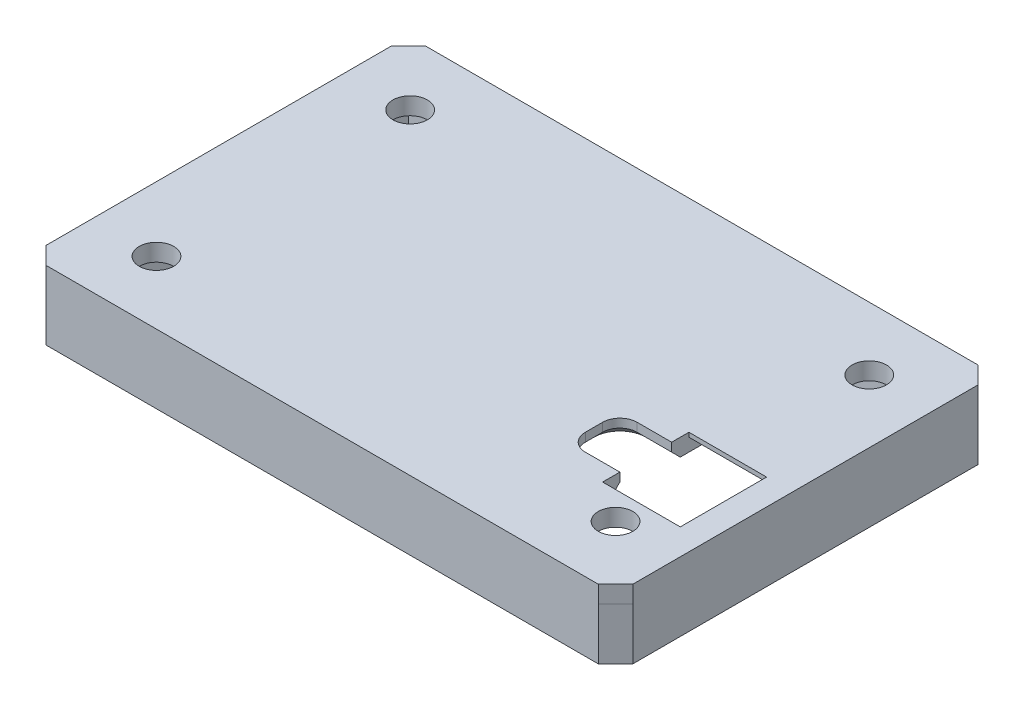
SolidWorks part; units mm, degrees
ref_plane "Front Plane" through (0, 0, 0) normal (0, 0, 1) x (1, 0, 0)
ref_plane "Top Plane" through (0, 0, 0) normal (0, 1, 0) x (1, 0, 0)
ref_plane "Right Plane" through (0, 0, 0) normal (1, 0, 0) x (0, 0, -1)
sketch "Sketch1" plane through (0, 0, 0) normal (0, 1, 0) x (1, 0, 0)
  line L1 (-29.6081, 14.5531) -> (38.3919, 14.5531)
  line L2 (-29.6081, 14.5531) -> (-29.6081, -29.4469)
  line L3 (-29.6081, -29.4469) -> (38.3919, -29.4469)
  line L4 (38.3919, 14.5531) -> (38.3919, -29.4469)
  dimension "D1" = 68
  dimension "D2" = 44
extrude "Boss-Extrude1" add sketch "Sketch1" along normal blind 2
sketch "Sketch2" plane through (0, 2, 0) normal (0, 1, 0) x (1, 0, 0)
  line L0 (38.3919, 14.5531) -> (-29.6081, 14.5531) construction
  line L1 (-29.6081, 14.5531) -> (-29.6081, -29.4469) construction
  line L2 (38.3919, -29.4469) -> (38.3919, 14.5531) construction
  line L3 (-29.6081, -29.4469) -> (38.3919, -29.4469) construction
  circle A0 centre (-22.1081, 7.2531) radius 2
  circle A1 centre (31.0919, 7.2531) radius 2
  circle A2 centre (31.0919, -22.1469) radius 2
  circle A3 centre (-22.1081, -22.1469) radius 2
  dimension "D1" = 4
  dimension "D2" = 4
  dimension "D3" = 4
  dimension "D4" = 4
  dimension "D5" = 7.3
  dimension "D6" = 7.5
  dimension "D7" = 7.3
  dimension "D8" = 7.3
  dimension "D9" = 7.3
  dimension "D10" = 7.3
  dimension "D11" = 7.3
  dimension "D12" = 7.5
extrude "Cut-Extrude1" cut sketch "Sketch2" against normal blind 2
sketch "Sketch3" plane through (0, 2, 0) normal (0, 1, 0) x (1, 0, 0)
  line L0 (38.3919, -29.4469) -> (38.3919, 14.5531) construction
  line L1 (38.3919, 4.0531) -> (26.3919, 4.0531)
  line L2 (38.3919, 4.0531) -> (38.3919, -18.9469)
  line L3 (38.3919, -18.9469) -> (26.3919, -18.9469)
  line L4 (26.3919, 4.0531) -> (26.3919, -18.9469)
  line L5 (38.3919, 14.5531) -> (-29.6081, 14.5531) construction
  dimension "D1" = 12
  dimension "D2" = 23
  dimension "D3" = 10.5
extrude "Cut-Extrude2" cut sketch "Sketch3" against normal blind 2
sketch "Sketch4" plane through (0, 2, 0) normal (0, 1, 0) x (1, 0, 0)
  line L0 (26.3919, -18.9469) -> (38.3919, -18.9469) construction
  line L1 (38.3919, 4.0531) -> (35.3919, 4.0531)
  line L2 (38.3919, 4.0531) -> (38.3919, -18.9469)
  line L3 (38.3919, -18.9469) -> (35.3919, -18.9469)
  line L4 (35.3919, 4.0531) -> (35.3919, -18.9469)
  dimension "D1" = 3
extrude "Boss-Extrude2" add sketch "Sketch4" against normal blind 2
sketch "Sketch8" plane through (0, 2, 0) normal (0, 1, 0) x (1, 0, 0)
  line L0 (-29.6081, 14.5531) -> (-29.6081, -29.4469) construction
  line L1 (-29.6081, -13.4469) -> (-23.6081, -13.4469)
  line L2 (-29.6081, -13.4469) -> (-29.6081, -1.4469)
  line L3 (-29.6081, -1.4469) -> (-23.6081, -1.4469)
  line L4 (-23.6081, -13.4469) -> (-23.6081, -1.4469)
  line L5 (38.3919, 14.5531) -> (-29.6081, 14.5531) construction
  line L6 (-29.6081, -29.4469) -> (38.3919, -29.4469) construction
  dimension "D1" = 16
  dimension "D2" = 16
  dimension "D3" = 6
extrude "Cut-Extrude4" cut sketch "Sketch8" against normal blind 20
chamfer "Chamfer2" distance 1 angle 45 2 edges at (-29.6081, 1, 1.4469) (-29.6081, 1, 13.4469)
chamfer "Chamfer4" distance 2 angle 45 4 edges at (38.3919, 1, 29.4469) (38.3919, 1, -14.5531) (-29.6081, 1, -14.5531) (-29.6081, 1, 29.4469)
sketch "Sketch9" plane through (0, 0, 0) normal (0, -1, 0) x (1, 0, 0)
  line L0 (38.3919, 27.4469) -> (38.3919, -12.5531) construction
  line L1 (-29.6081, -14.5531) -> (38.3919, -14.5531)
  line L2 (-29.6081, -14.5531) -> (-29.6081, -11.5531)
  line L3 (-26.6081, -11.5531) -> (35.3919, -11.5531)
  line L4 (38.3919, -14.5531) -> (38.3919, -11.5531)
  line L5 (-29.6081, 14.4469) -> (-29.6081, 27.4469) construction
  line L6 (38.3919, 29.4469) -> (-29.6081, 29.4469)
  line L7 (38.3919, 29.4469) -> (38.3919, 25.7643)
  line L8 (35.3919, 26.4469) -> (-26.6081, 26.4469)
  line L9 (-29.6081, 29.4469) -> (-29.6081, 25.7643)
  line L10 (-27.6081, 29.4469) -> (36.3919, 29.4469) construction
  line L12 (38.3919, -11.5531) -> (38.3919, 25.7643)
  line L14 (35.3919, -11.5531) -> (35.3919, 26.4469)
  line L16 (-29.6081, -11.5531) -> (-29.6081, 25.7643)
  line L18 (-26.6081, -11.5531) -> (-26.6081, 26.4469)
  dimension "D1" = 3
  dimension "D2" = 3
  dimension "D3" = 3
  dimension "D4" = 0
extrude "Boss-Extrude5" add sketch "Sketch9" along normal blind 6
chamfer "Chamfer5" distance 2 angle 45 4 edges at (38.3919, -3, 29.4469) (-29.6081, -3, 29.4469) (-29.6081, -3, -14.5531) (38.3919, -3, -14.5531)
sketch "Sketch12" plane through (0, 2, 0) normal (0, 1, 0) x (1, 0, 0)
  line L0 (-29.6081, 12.5531) -> (-29.6081, -0.4469) construction
  line L1 (-29.6081, 1.619) -> (-21.2317, 1.619)
  line L2 (-29.6081, 1.619) -> (-29.6081, -16.605)
  line L3 (-29.6081, -16.605) -> (-21.2317, -16.605)
  line L4 (-21.2317, 1.619) -> (-21.2317, -16.605)
extrude "Boss-Extrude10" add sketch "Sketch12" against normal blind 2
sketch "Sketch15" plane through (26.3919, 0, 0) normal (1, 0, 0) x (0, 0, -1)
  line L0 (4.0531, 0) -> (-18.9469, 0) construction
  line L1 (-8.9469, 0.5) -> (-5.9469, 0.5)
  line L2 (-8.9469, 0.5) -> (-8.9469, 2)
  line L3 (-8.9469, 2) -> (-5.9469, 2)
  line L4 (-5.9469, 0.5) -> (-5.9469, 2)
  line L5 (4.0531, 2) -> (-18.9469, 2) construction
  line L6 (-18.9469, 0) -> (-18.9469, 2) construction
  line L7 (4.0531, 0) -> (4.0531, 2) construction
  point P8 (-7.4469, 2)
  dimension "D1" = 0.5
  dimension "D2" = 0
  dimension "D3" = 10
  dimension "D4" = 10
extrude "Boss-Extrude11" add sketch "Sketch15" along normal blind 12
chamfer "Chamfer7" distance 1 angle 45 2 edges at (30.8919, 0.5, 5.9469) (30.8919, 0.5, 8.9469)
sketch "Sketch16" plane through (0, 0, 5.9469) normal (0, 0, -1) x (-1, 0, 0)
  line L1 (-26.3919, 1.5) -> (-35.3919, 1.5)
  line L2 (-26.3919, 1.5) -> (-26.3919, 2)
  line L3 (-26.3919, 2) -> (-35.3919, 2)
  line L4 (-35.3919, 1.5) -> (-35.3919, 2)
extrude "Boss-Extrude12" add sketch "Sketch16" along normal blind 11
sketch "Sketch17" plane through (0, 2, 0) normal (0, 1, 0) x (1, 0, 0)
  line L0 (26.3919, -8.9469) -> (26.3919, -18.9469) construction
  line L1 (26.3919, -16.9469) -> (20.3919, -16.9469)
  line L2 (26.3919, -16.9469) -> (26.3919, -10.9469)
  line L3 (26.3919, -10.9469) -> (20.3919, -10.9469)
  line L4 (20.3919, -16.9469) -> (20.3919, -10.9469)
  line L5 (26.3919, -18.9469) -> (35.3919, -18.9469) construction
  line L6 (35.3919, -8.9469) -> (26.3919, -8.9469) construction
  dimension "D1" = 2
  dimension "D2" = 2
  dimension "D3" = 6
extrude "Cut-Extrude5" cut sketch "Sketch17" against normal blind 11
fillet "Fillet1" radius 2 2 edges at (20.3919, 1, 10.9469) (20.3919, 1, 16.9469)
sketch "Sketch18" plane through (-29.6081, 0, 0) normal (-1, 0, 0) x (0, 0, 1)
  line L0 (27.4469, -6) -> (-12.5531, -6) construction
  line L1 (1.9469, -6) -> (12.9469, -6)
  line L2 (1.9469, -6) -> (1.9469, -3)
  line L3 (1.9469, -3) -> (12.9469, -3)
  line L4 (12.9469, -6) -> (12.9469, -3)
  line L6 (27.4469, -6) -> (27.4469, 0) construction
  dimension "D1" = 11
  dimension "D2" = 3
  dimension "D3" = 14.5
extrude "Cut-Extrude6" cut sketch "Sketch18" against normal blind 1
chamfer "Chamfer8" distance 1 angle 45 3 edges at (-29.6081, -4.5, 12.9469) (-29.6081, -3, 7.4469) (-29.6081, -4.5, 1.9469)
sketch "Sketch19" plane through (-28.6081, 0, 0) normal (-1, 0, 0) x (0, 0, 1)
  line L0 (1.9469, -6) -> (12.9469, -6) construction
  circle A0 centre (7.4469, -8.4) radius 3.25
  dimension "D1" = 6.5
  dimension "D2" = 2.4
extrude "Cut-Extrude7" cut sketch "Sketch19" against normal blind 11
sketch "Sketch20" plane through (0, 0, -14.5531) normal (0, 0, -1) x (-1, 0, 0)
  line L0 (-36.3919, 0) -> (-38.3919, 0) construction
  line L1 (-38.3919, -6) -> (-38.3919, 0) construction
  line L2 (27.6081, -6) -> (-36.3919, -6) construction
  line L4 (-23.1419, -2.75) -> (-23.1419, -6)
  line L5 (-23.1419, -6) -> (-17.6419, -6)
  line L6 (-17.6419, -2.75) -> (-17.6419, -6)
  arc A0 (-17.6419, -2.75) -> (-23.1419, -2.75) centre (-20.3919, -2.75) ccw
  dimension "D1" = 5.5
  dimension "D2" = 2.75
  dimension "D3" = 18
extrude "Cut-Extrude8" cut sketch "Sketch20" against normal blind 11
chamfer "Chamfer9" distance 1 angle 45 5 edges at (24.3919, 0, 10.9469) (24.3919, 0, 16.9469) (20.9777, 0, 11.5327) (20.9777, 0, 16.3611) (20.3919, 0, 13.9469)
